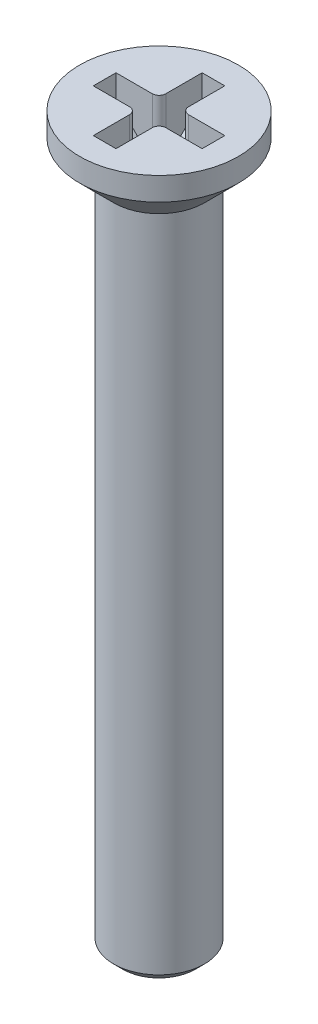
SolidWorks part; units mm, degrees
note: '?' marks a value the reader was unsure of.
material "AISI 304"
ref_plane "前视基准面" through (0, 0, 0) normal (0, 0, 1) x (1, 0, 0)
ref_plane "上视基准面" through (0, 0, 0) normal (0, 1, 0) x (1, 0, 0)
ref_plane "右视基准面" through (0, 0, 0) normal (1, 0, 0) x (0, 0, -1)
sketch "草图1" plane through (0, 0, 0) normal (0, 0, 1) x (1, 0, 0)
  line L0 (0, -3.7692) -> (0, 4.9978) construction
  line L1 (0, 2.6897) -> (-1.75, 2.6897)
  line L2 (-1.75, 2.6897) -> (-1.75, 2.1797)
  line L3 (-1.75, 2.1797) -> (-1, 1.4297)
  line L4 (-1, 1.4297) -> (-1, -13.1103)
  line L5 (-1, -13.1103) -> (-0.8, -13.3103)
  line L6 (-0.8, -13.3103) -> (0, -13.3103)
  line L7 (0, -13.3103) -> (0, 2.6897)
  dimension "D1" = 1.75
  dimension "D2" = 1.26
  dimension "D3" = 45
  dimension "D4" = 1
  dimension "D5" = 45
  dimension "D6" = 16
  dimension "D7" = 0.8
revolve "旋转1" add sketch "草图1" angle 360 about L0
sketch "草图2" plane through (0, 2.6897, 0) normal (0, 1, 0) x (1, 0, 0)
  line L0 (0, 0) -> (0, 1.9578) construction
  line L1 (0.25, 1.2) -> (-0.25, 1.2)
  line L2 (0.25, 1.2) -> (0.25, 0)
  line L3 (0.25, 0) -> (-0.25, 0)
  line L4 (-0.25, 1.2) -> (-0.25, 0)
  line L5 (0.25, 1.2) -> (-0.25, 0) construction
  line L6 (0.25, 0) -> (-0.25, 1.2) construction
  point P0 (0, 0.6)
  point P8 (0, 0.7405)
  dimension "D1" = 0.5
  dimension "D2" = 1.2
extrude "切除-拉伸1" cut sketch "草图2" against normal blind 0.5
sketch "草图3" plane through (-0.25, 0, 0) normal (1, 0, 0) x (0, 0, -1)
  line L0 (0, 2.1897) -> (0, 1.4297)
  line L1 (0.44, 1.4297) -> (1.2, 2.1897)
  line L3 (0, 2.1897) -> (1.2, 2.1897) construction
  line L4 (1, 1.4297) -> (1.75, 2.1797) construction
  line L5 (0, 1.4297) -> (0.44, 1.4297)
  line L7 (0, 2.1897) -> (1.2, 2.1897)
  line L8 (1, 1.4297) -> (-1, 1.4297) construction
  line L9 (1, 1.4297) -> (1.75, 2.1797) construction
  line L10 (1.2, 2.1897) -> (1.2, 2.6897) construction
  point P1 (0, 1.4804)
  point P14 (1.2, 2.1897)
extrude "切除-拉伸2" cut sketch "草图3" along normal blind 0.5
ref_axis "基准轴1" through (0, 1.4297, 0) along (0, -1, 0)?
pattern_circular "阵列(圆周)1" count 4 over 360 about axis through (0, 0, 0) along (0, 1, 0) of "切除-拉伸1", "切除-拉伸2"
fillet "圆角1" radius 0.15 4 edges at (0.25, 2.0597, -0.25) (-0.25, 2.0597, -0.25) (0.25, 2.0597, 0.25) (-0.25, 2.0597, 0.25)
